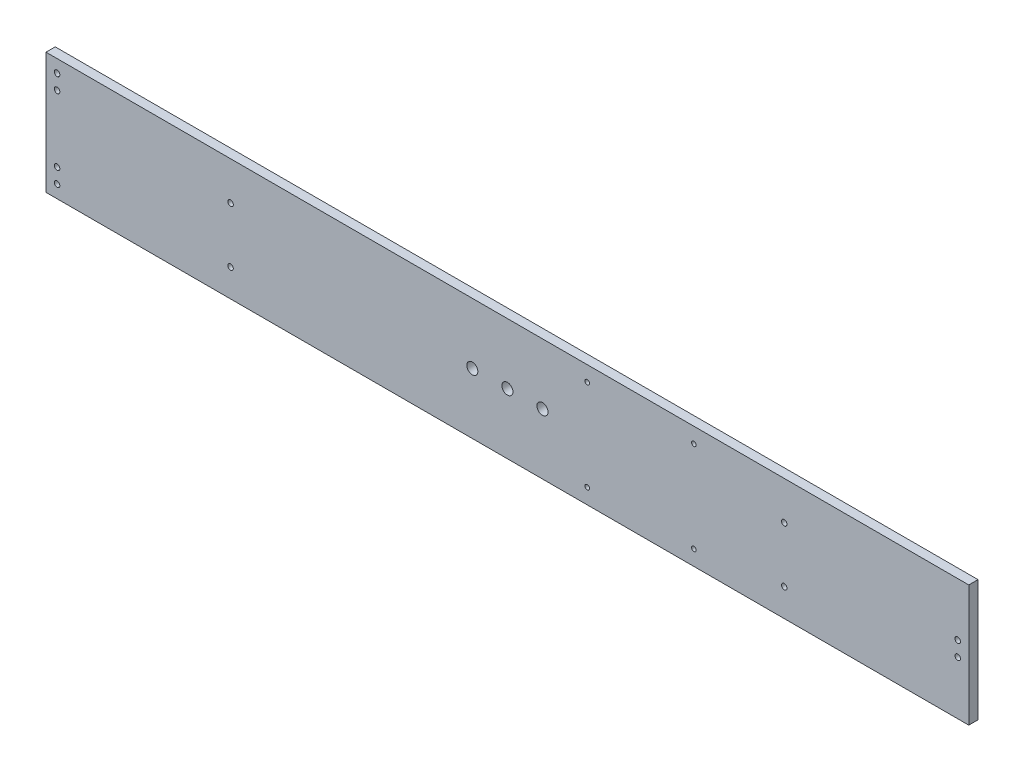
SolidWorks part; units mm, degrees
ref_plane "前视基准面" through (0, 0, 0) normal (0, 0, 1) x (1, 0, 0)
ref_plane "上视基准面" through (0, 0, 0) normal (0, 1, 0) x (1, 0, 0)
ref_plane "右视基准面" through (0, 0, 0) normal (1, 0, 0) x (0, 0, -1)
sketch "草图3" plane through (0, 0, 0) normal (0, 0, 1) x (1, 0, 0)
  line L1 (250, -32.9) -> (-250, -32.9)
  line L2 (250, -32.9) -> (250, 32.9)
  line L3 (250, 32.9) -> (-250, 32.9)
  line L4 (-250, -32.9) -> (-250, 32.9)
  line L5 (250, -32.9) -> (-250, 32.9) construction
  line L6 (250, 32.9) -> (-250, -32.9) construction
  line L7 (125, -27.9) -> (40, -27.9) construction
  line L8 (125, -27.9) -> (125, 27.9) construction
  line L9 (125, 27.9) -> (40, 27.9) construction
  line L10 (40, -27.9) -> (40, 27.9) construction
  line L11 (125, -27.9) -> (40, 27.9) construction
  line L12 (125, 27.9) -> (40, -27.9) construction
  line L13 (-30, -3) -> (30, -3) construction
  line L14 (-30, -3) -> (-30, 3) construction
  line L15 (-30, 3) -> (30, 3) construction
  line L16 (30, -3) -> (30, 3) construction
  line L17 (-30, -3) -> (30, 3) construction
  line L18 (-30, 3) -> (30, -3) construction
  circle A0 centre (43.25, 24.65) radius 1.25
  circle A1 centre (43.25, -24.65) radius 1.25
  circle A2 centre (101.05, -24.65) radius 1.25
  circle A3 centre (101.05, 24.65) radius 1.25
  circle A4 centre (0, 0) radius 3
  point P0 (0, 0)
  point P6 (82.5, 0)
  point P19 (0, 0)
  dimension "D9" = 2.5
  dimension "D12" = 2.5
  dimension "D14" = 2.5
  dimension "D16" = 2.5
  dimension "D21" = 6
  dimension "D1" = 500
  dimension "D2" = 55.8
  dimension "D3" = 5
  dimension "D4" = 5
  dimension "D5" = 85
  dimension "D6" = 40
  dimension "D7" = 3.25
  dimension "D8" = 3.25
  dimension "D10" = 3.25
  dimension "D11" = 3.25
  dimension "D13" = 3.25
  dimension "D15" = 57.8
  dimension "D17" = 60
  dimension "D18" = 0
  dimension "D19" = 6
  dimension "D20" = 0
extrude "凸台-拉伸2" add sketch "草图3" along normal blind 5
sketch "草图4" plane through (0, 0, 5) normal (0, 0, 1) x (1, 0, 0)
  line L0 (-250, -32.9) -> (250, -32.9) construction
  line L3 (0, 32.9) -> (0, -32.9) construction
  line L4 (250, 32.9) -> (-250, 32.9) construction
  circle A0 centre (150, 12.1) radius 1.5
  circle A1 centre (150, -17.9) radius 1.5
  circle A2 centre (-150, -17.9) radius 1.5
  circle A3 centre (-150, 12.1) radius 1.5
  dimension "D1" = 3
  dimension "D2" = 3
  dimension "D3" = 150
  dimension "D4" = 30
  dimension "D5" = 15
extrude "切除-拉伸1" cut sketch "草图4" against normal blind 5
sketch "草图5" plane through (0, 0, 5) normal (0, 0, 1) x (1, 0, 0)
  line L0 (250, 32.9) -> (-250, 32.9) construction
  line L1 (-250, 32.9) -> (-250, -32.9) construction
  line L2 (-244, 26) -> (-244, 4) construction
  line L3 (-250, -32.9) -> (250, -32.9) construction
  line L4 (0, 32.9) -> (0, -32.9) construction
  line L5 (244, 26) -> (244, 4) construction
  circle A0 centre (-244, 26) radius 1.5
  circle A12 centre (-244, 18) radius 1.5
  circle A13 centre (-244, 4) radius 1.5
  circle A14 centre (-244, -4) radius 1.5
  circle A15 centre (-244, -18) radius 1.5
  circle A16 centre (-244, -26) radius 1.5
  circle A23 centre (244, -26) radius 1.5
  circle A24 centre (244, -18) radius 1.5
  circle A25 centre (244, -4) radius 1.5
  circle A26 centre (244, 4) radius 1.5
  circle A27 centre (244, 18) radius 1.5
  circle A28 centre (244, 26) radius 1.5
  dimension "D1" = 3
  dimension "D4" = 3
  dimension "D2" = 6.9
  dimension "D3" = 6
  dimension "D5" = 8
  dimension "D6" = 3
  dimension "D7" = 22
extrude "切除-拉伸2" cut sketch "草图5" against normal blind 5 contours A0 | A12 | A26 | A15 | A16 | A25 region at (-244, 26, 5) region at (-244, 18, 5) region at (-244, -18, 5) region at (-244, -26, 5) region at (244, -4, 5) region at (244, 4, 5)
sketch "草图6" plane through (0, 0, 5) normal (0, 0, 1) x (1, 0, 0)
  circle A0 centre (19, 0) radius 3
  circle A1 centre (-19, 0) radius 3
  dimension "D3" = 6
  dimension "D4" = 6
  dimension "D1" = 19
  dimension "D2" = 19
extrude "切除-拉伸3" cut sketch "草图6" against normal blind 10
